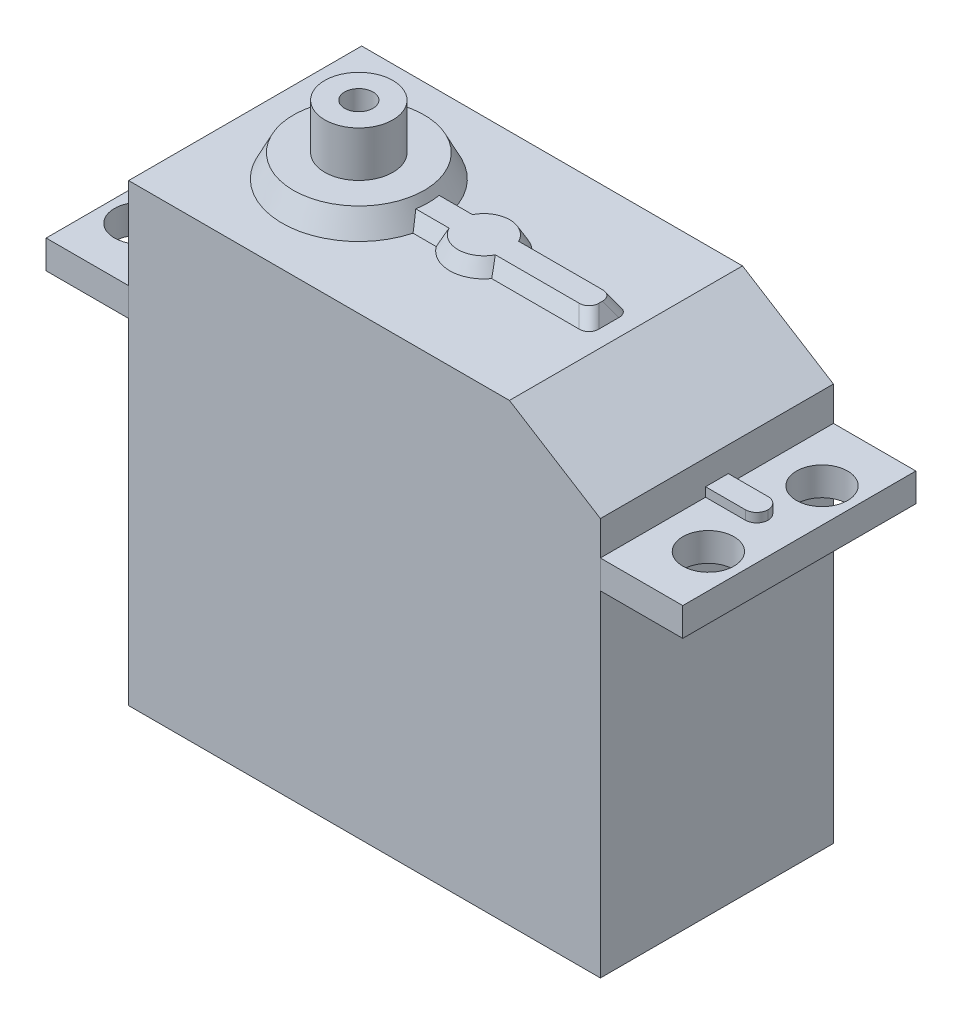
SolidWorks part; units mm, degrees
ref_plane "Front Plane" through (0, 0, 0) normal (0, 0, 1) x (1, 0, 0)
ref_plane "Top Plane" through (0, 0, 0) normal (0, 1, 0) x (1, 0, 0)
ref_plane "Right Plane" through (0, 0, 0) normal (1, 0, 0) x (0, 0, -1)
sketch "Sketch1" plane through (0, 0, 0) normal (0, 1, 0) x (1, 0, 0)
  line L1 (-10, 10.25) -> (31.5, 10.25)
  line L2 (-10, 10.25) -> (-10, -10.25)
  line L3 (-10, -10.25) -> (31.5, -10.25)
  line L4 (31.5, 10.25) -> (31.5, -10.25)
  circle A0 centre (0, 0) radius 1.25
  dimension "D1" = 10
  dimension "D2" = 41.5
  dimension "D3" = 10.25
  dimension "D4" = 20.5
extrude "Boss-Extrude1" add sketch "Sketch1" against normal blind 40
chamfer "Chamfer1" distance 5 distance2 8 1 edges at (31.5, 0, 0) first distance on face at (31.5, -20, 0)
ref_plane "Plane1" through (0, -8, 0) normal (0, 1, 0) x (1, 0, 0)
sketch "Sketch2" plane through (0, -8, 0) normal (0, 1, 0) x (1, 0, 0)
  line L0 (-17.25, -0.0031) -> (38.75, -0.0031) construction
  line L1 (-10, 10.25) -> (-17.25, 10.25)
  line L2 (-10, 10.25) -> (-10, -10.2561)
  line L3 (-10, -10.2561) -> (-17.25, -10.2561)
  line L4 (-17.25, 10.25) -> (-17.25, -10.2561)
  line L5 (31.5, 10.25) -> (38.75, 10.25)
  line L6 (31.5, 10.25) -> (31.5, -10.2561)
  line L7 (31.5, -10.2561) -> (38.75, -10.2561)
  line L8 (38.75, 10.25) -> (38.75, -10.2561)
  line L9 (38.75, -0.0031) -> (10.75, -0.0031) construction
  line L10 (10.75, -0.0031) -> (10.75, 6.339) construction
  circle A0 centre (-14.25, 4.9969) radius 2.25
  circle A1 centre (35.75, 4.9969) radius 2.25
  circle A2 centre (35.75, -5.0031) radius 2.25
  circle A3 centre (-14.25, -5.0031) radius 2.25
  dimension "D4" = 4.5
  dimension "D1" = 7.25
  dimension "D2" = 7.25
  dimension "D3" = 25
  dimension "D5" = 5
extrude "Boss-Extrude2" add sketch "Sketch2" against normal blind 2.5
sketch "Sketch3" plane through (0, -8, 0) normal (0, 1, 0) x (1, 0, 0)
  line L0 (-10, -10.25) -> (-10, 10.25) construction
  line L1 (-14.5, 1) -> (36, 1)
  line L2 (-14.5, 1) -> (-14.5, -1)
  line L3 (-14.5, -1) -> (36, -1)
  line L4 (36, 1) -> (36, -1)
  line L5 (31.5, 10.25) -> (31.5, -10.25) construction
  dimension "D1" = 1
  dimension "D2" = 2
  dimension "D3" = 4.5
  dimension "D4" = 4.5
extrude "Boss-Extrude3" add sketch "Sketch3" along normal blind 0.8
fillet "Fillet1" radius 1 4 edges at (36, -7.6, 1) (36, -7.6, -1) (-14.5, -7.6, -1) (-14.5, -7.6, 1)
sketch "Sketch4" plane through (0, 0, 0) normal (0, 1, 0) x (1, 0, 0)
  circle A0 centre (0, 0) radius 6.75
extrude "Boss-Extrude4" add sketch "Sketch4" along normal blind 2
chamfer "Chamfer2" distance 2 distance2 1 1 edges at (0, 2, 6.75) first distance on face at (0, 2, 6.75)
sketch "Sketch5" plane through (0, 0, 0) normal (0, 1, 0) x (1, 0, 0)
  line L0 (13.4367, 1.75) -> (22, 1.75)
  line L1 (2.9829, 1.75) -> (8.5633, 1.75)
  line L2 (2.9829, 1.75) -> (2.9829, -1.75)
  line L3 (2.9829, -1.75) -> (8.5633, -1.75)
  line L4 (22, 1.75) -> (22, -1.75)
  line L5 (13.4367, -1.75) -> (22, -1.75)
  arc A0 (8.5633, -1.75) -> (13.4367, -1.75) centre (11, 0) ccw
  arc A1 (13.4367, 1.75) -> (8.5633, 1.75) centre (11, 0) ccw
  dimension "D5" = 6
  dimension "D1" = 1.75
  dimension "D2" = 3.5
  dimension "D3" = 22
  dimension "D4" = 11
extrude "Boss-Extrude5" add sketch "Sketch5" along normal blind 1.25 draft 30 contours L1 A1 L0 L4 L5 A0 L3 L2
fillet "Fillet2" radius 1 2 edges at (21.6392, 0.625, 1.3892) (21.6392, 0.625, -1.3892)
sketch "Sketch6" plane through (0, 0, 0) normal (0, 1, 0) x (1, 0, 0)
  circle A0 centre (0, 0) radius 3
  circle A1 centre (0, 0) radius 1.25
extrude "Boss-Extrude6" add sketch "Sketch6" along normal blind 6
sketch "Sketch7" plane through (-10, 0, 0) normal (-1, 0, 0) x (0, 0, 1)
  line L0 (-10.25, -40) -> (10.25, -40) construction
  line L1 (-3.5, -31) -> (3.5, -31)
  line L2 (-3.5, -31) -> (-3.5, -35.5)
  line L3 (-3.5, -35.5) -> (3.5, -35.5)
  line L4 (3.5, -31) -> (3.5, -35.5)
  circle A0 centre (0, -22) radius 2
  dimension "D5" = 18
  dimension "D1" = 7
  dimension "D2" = 3.5
  dimension "D3" = 4.5
  dimension "D4" = 4.5
extrude "Boss-Extrude7" add sketch "Sketch7" along normal blind 5
